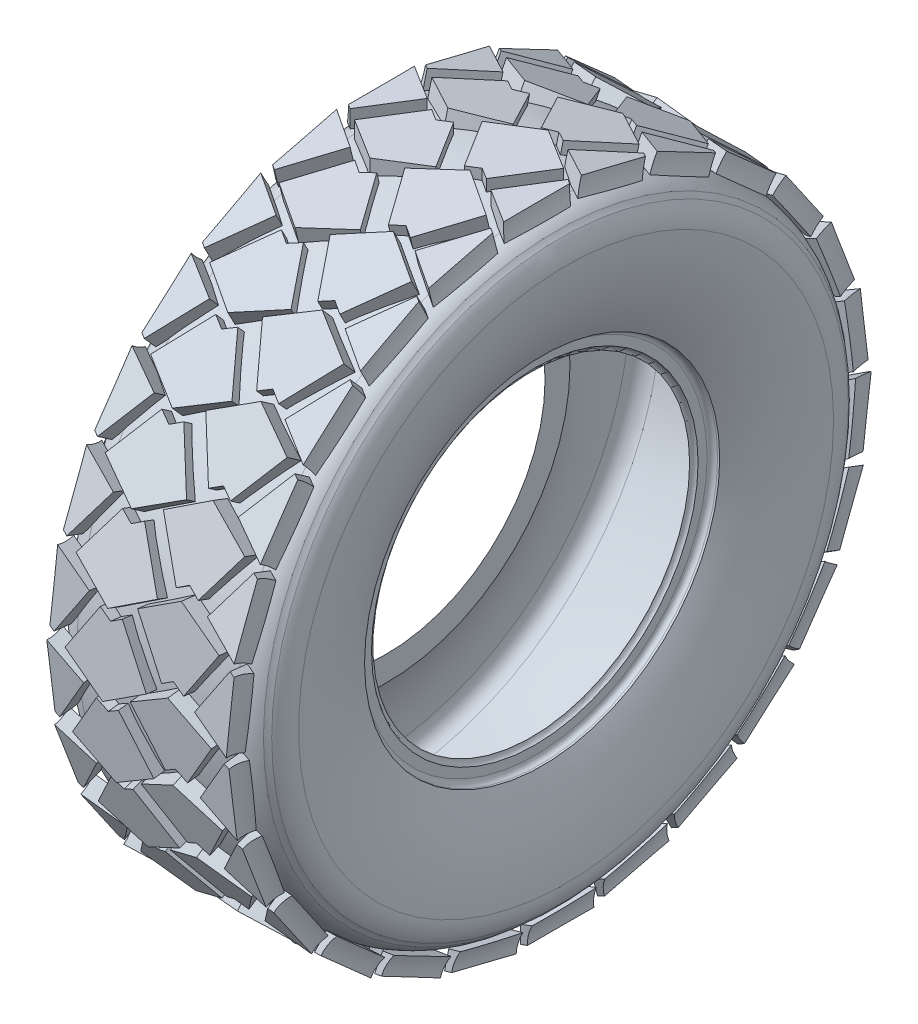
SolidWorks part; units mm, degrees
note: The reader was unsure of these and kept them because the rebuilt part matched: shared geometry of "Sketch6<3>".
ref_plane "Front Plane" through (0, 0, 0) normal (0, 0, 1) x (1, 0, 0)
ref_plane "Top Plane" through (0, 0, 0) normal (0, 1, 0) x (1, 0, 0)
ref_plane "Right Plane" through (0, 0, 0) normal (1, 0, 0) x (0, 0, -1)
sketch "Sketch1" plane through (0, 0, 0) normal (0, 0, 1) x (1, 0, 0)
  line L0 (0, 355) -> (0, -355) construction
  line L2 (-122.5, 314.5516) -> (-122.5, 344.2783) construction
  line L16 (122.5, 314.5516) -> (122.5, 366.3353) construction
  line L17 (95, 203) -> (92.6042, 203)
  line L18 (-82.6042, 209.5072) -> (-82.6042, 181)
  line L19 (-86.6042, 186.6569) -> (-86.6042, 197)
  line L20 (86.6042, 186.6569) -> (86.6042, 197)
  line L21 (-95, 203) -> (-92.6042, 203)
  line L22 (82.6042, 209.5072) -> (82.6042, 181)
  line L23 (165.1761, 0) -> (-186.3873, 0) construction
  arc A6 (-89.8534, 346.515) -> (89.8534, 346.515) centre (0, -125) cw
  arc A7 (-92.2595, 323.6114) -> (92.2595, 323.6114) centre (0, -125) cw
  arc A12 (-261.6885, 250.8765) -> (92.2595, 323.6114) centre (0, -125) cw construction
  arc A13 (-274.2587, 268.9317) -> (96.6912, 345.1604) centre (0, -125) cw construction
  arc A14 (-122.3388, 305.7561) -> (-95, 203) centre (117.5, 314.5516) ccw
  arc A15 (-108.2045, 302.999) -> (-82.6042, 209.5072) centre (117.5, 314.5516) ccw
  arc A16 (-102.8806, 364.6354) -> (-82.6042, 209.5072) centre (117.5, 314.5516) ccw construction
  arc A17 (122.3388, 305.7561) -> (95, 203) centre (-117.5, 314.5516) cw
  arc A18 (-92.2595, 323.6114) -> (-108.2045, 302.999) centre (-88.2307, 304.0214) ccw
  arc A19 (122.3388, 305.7561) -> (89.8534, 346.515) centre (82.3657, 307.222) ccw
  arc A20 (-116.5325, 367.7379) -> (-95, 203) centre (117.5, 314.5516) ccw construction
  arc A21 (-89.8534, 346.515) -> (-122.3388, 305.7561) centre (-82.3657, 307.222) ccw
  arc A22 (92.2595, 323.6114) -> (108.2045, 302.999) centre (88.2307, 304.0214) cw
  arc A23 (108.2045, 302.999) -> (82.6042, 209.5072) centre (-117.5, 314.5516) cw
  arc A24 (-82.6042, 181) -> (-86.6042, 186.6569) centre (-88.6042, 181) ccw
  arc A25 (-86.6042, 197) -> (-92.6042, 203) centre (-92.6042, 197) ccw
  arc A26 (86.6042, 197) -> (92.6042, 203) centre (92.6042, 197) cw
  arc A27 (82.6042, 181) -> (86.6042, 186.6569) centre (88.6042, 181) cw
  point P1 (0, 0)
  point P9 (0, 355)
  point P47 (-93.8021, 203)
  dimension "D1" = 480
  dimension "D2" = 22
  dimension "D3" = 458
  dimension "D4" = 240
  dimension "D6" = 40
  dimension "D9" = 6
  dimension "D10" = 22
  dimension "D13" = 190
  dimension "D7" = 20
  dimension "D11" = 6
  dimension "D12" = 4
  dimension "D14" = 152
  dimension "D5" = 14
  dimension "D8" = 245
  dimension "D15" = 203
revolve "Revolve1" add sketch "Sketch1" angle 360 about L23
ref_plane "Plane2" through (0, 345, 0) normal (0, 1, 0) x (1, 0, 0)
sketch "Sketch3" plane through (0, 345, 0) normal (0, 1, 0) x (1, 0, 0)
  line L0 (0, 355) -> (0, -355) construction
  line L1 (-122.3657, 0) -> (122.3657, 0) construction
  line L2 (-122.3657, 307.222) -> (-122.3657, -307.222) construction
  line L3 (122.3657, -307.222) -> (122.3657, 307.222) construction
  line L4 (-122.3657, 26.17) -> (-37.2148, -27.0381) construction
  line L5 (-37.2148, -27.0381) -> (37.2148, 27.0381) construction
  line L6 (37.2148, 27.0381) -> (122.3657, -26.17) construction
  line L7 (-122.3657, 63.9038) -> (-63.3708, 27.0397)
  line L8 (122.3657, -307.222) -> (122.3657, 307.222)
  line L9 (-63.3708, 27.0397) -> (-97.2857, -27.2354)
  line L10 (-122.3657, -11.5637) -> (-97.2857, -27.2354)
  line L11 (-122.3657, 307.222) -> (-122.3657, -307.222)
  line L12 (-122.3657, 63.9038) -> (-122.3657, -11.5637)
  line L13 (122.3657, 11.5637) -> (97.2857, 27.2354)
  line L14 (97.2857, 27.2354) -> (63.3708, -27.0397)
  line L15 (122.3657, -63.9038) -> (63.3708, -27.0397)
  line L16 (122.3657, 11.5637) -> (122.3657, -63.9038)
  line L18 (-49.802, 18.561) -> (-83.7169, -35.7141)
  line L19 (83.7169, 35.7141) -> (49.802, -18.561)
  line L20 (83.7169, 35.7141) -> (37.2148, 64.7718)
  line L22 (63.3708, -27.0397) -> (37.2148, -10.6956) construction
  line L25 (37.2148, 87.9621) -> (37.2148, -44.5917) construction
  line L27 (49.802, -18.561) -> (37.2148, -10.6956)
  line L28 (24.6275, -18.561) -> (37.2148, -10.6956)
  line L29 (-9.2873, 35.7141) -> (24.6275, -18.561)
  line L30 (-9.2873, 35.7141) -> (37.2148, 64.7718)
  line L31 (-80.3282, 37.6359) -> (-63.3708, 27.0397) construction
  line L32 (-109.8257, -19.3995) -> (-97.2857, -27.2354) construction
  line L33 (28.4868, 59.318) -> (-43.27, 14.4793) construction
  line L34 (-37.2148, 10.6956) -> (-37.2148, -64.7718) construction
  line L35 (-49.802, 18.561) -> (-37.2148, 10.6956)
  line L36 (-83.7169, -35.7141) -> (-37.2148, -64.7718)
  line L37 (9.2873, -35.7141) -> (-37.2148, -64.7718)
  line L38 (-24.6275, 18.561) -> (9.2873, -35.7141)
  line L39 (-24.6275, 18.561) -> (-37.2148, 10.6956)
  line L40 (63.3708, -27.0397) -> (49.802, -18.561)
  line L41 (97.2857, 27.2354) -> (83.7169, 35.7141)
  line L42 (9.2873, -35.7141) -> (24.6275, -18.561)
  line L43 (-24.6275, 18.561) -> (-9.2873, 35.7141)
  line L44 (-49.802, 18.561) -> (-63.3708, 27.0397)
  line L45 (-83.7169, -35.7141) -> (-97.2857, -27.2354)
  arc A0 (89.8534, 346.515) -> (-89.8534, 346.515) centre (0, -125) ccw construction
  arc A1 (-89.8534, -346.515) -> (89.8534, -346.515) centre (0, 125) ccw construction
  point P21 (0, 0)
  point P24 (-80.3282, -0.0978)
  point P30 (80.3282, 0.0978)
  dimension "D1" = 32
  dimension "D2" = 58
  dimension "D3" = 54
  dimension "D4" = 92
  dimension "D5" = 122
  dimension "D6" = 25.08
  dimension "D8" = 32
  dimension "D9" = 16
  dimension "D10" = 16
  dimension "D7" = 25.08
  dimension "D12" = 14.8426
extrude "Boss-Extrude4" add sketch "Sketch3" along normal blind 20 separate body contours L38 L39 L35 L18 L36 L37 | L7 L11 L10 L9 | L30 L29 L28 L27 L19 L20 | L15 L8 L13 L14
pattern_circular "CirPattern1" count 26 over 360 about axis through (0, 0, 0) along (1, 0, 0)
sketch "Sketch6" plane through (0, 0, 0) normal (0, 0, 1) x (1, 0, 0)
  line L0 (-97.4604, 343.9399) -> (-97.4604, 306.9363)
  line L1 (-97.4604, 306.9363) -> (-122.2703, 306.9359)
  line L2 (-143.3448, 314.4368) -> (-143.3448, 379.7397)
  line L3 (-143.3448, 379.7397) -> (-105.1104, 379.7397)
  line L4 (-280.3332, 0) -> (242.5413, 0) construction
  line L5 (0, 462.7964) -> (0, -463.2106) construction
  line L6 (97.4604, 306.9363) -> (122.2703, 306.9359)
  line L7 (97.4604, 343.9399) -> (97.4604, 306.9363)
  line L8 (143.3448, 314.4368) -> (143.3448, 379.7397)
  line L9 (143.3448, 379.7397) -> (105.1104, 379.7397)
  arc A0 (-97.4604, 343.9399) -> (-122.2703, 306.9359) centre (-82.2703, 306.9363) ccw
  arc A1 (-105.1104, 379.7397) -> (-143.3448, 314.4368) centre (-151.9499, 363.3195) cw
  arc A2 (97.4604, 343.9399) -> (122.2703, 306.9359) centre (82.2703, 306.9363) cw
  arc A3 (105.1104, 379.7397) -> (143.3448, 314.4368) centre (151.9499, 363.3195) ccw
  dimension "D1" = 40
revolve "Cut-Revolve1" cut sketch "Sketch6" angle 360 about L4
revolve "Cut-Revolve2" cut sketch "Sketch6<3>" angle 360 about L4
sketch "Sketch6<3>" plane through (0, 0, 0) normal (0, 0, 1) x (1, 0, 0) same geometry as "Sketch6"
